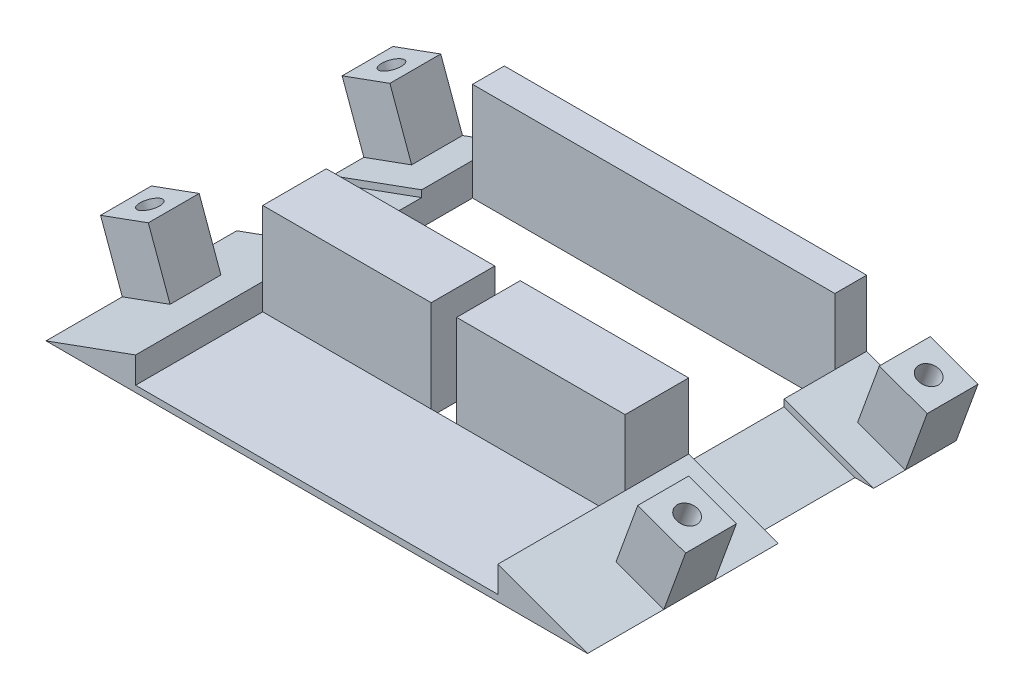
SolidWorks part; units mm, degrees
ref_plane "Front Plane" through (0, 0, 0) normal (0, 0, 1) x (1, 0, 0)
ref_plane "Top Plane" through (0, 0, 0) normal (0, 1, 0) x (1, 0, 0)
ref_plane "Right Plane" through (0, 0, 0) normal (1, 0, 0) x (0, 0, -1)
ref_plane "Plane2" through (28.5, 0, 0) normal (1, 0, 0) x (0, 0, -1)
sketch "Sketch2" plane through (0, 0, 0) normal (0, 0, 1) x (1, 0, 0)
  line L0 (-14.0954, 0) -> (0, 5.1303)
  line L1 (0, 5.1303) -> (0, 0)
  line L2 (-14.0954, 0) -> (0, 0)
  line L3 (28.5, -10.175) -> (28.5, 10.175) construction
  line L4 (71.0954, 0) -> (57, 5.1303)
  line L5 (57, 5.1303) -> (57, 0)
  line L6 (71.0954, 0) -> (57, 0)
  dimension "D1" = 20
  dimension "D2" = 15
extrude "Boss-Extrude1" add sketch "Sketch2" along normal blind 30 and the other way blind 28
sketch "Sketch3" plane through (0, 0, 0) normal (0, 0, 1) x (1, 0, 0)
  line L1 (57, 0) -> (0, 0)
  line L2 (57, 0) -> (57, 15.5)
  line L3 (57, 15.5) -> (0, 15.5)
  line L4 (0, 0) -> (0, 15.5)
  dimension "D1" = 15.5
extrude "Boss-Extrude2" add sketch "Sketch3" along normal blind 10
ref_plane "Plane3" through (0, 0, 15) normal (0, 0, -1) x (-1, 0, 0)
ref_plane "Plane4" through (0, 0, -23) normal (0, 0, 1) x (1, 0, 0)
sketch "Sketch4" plane through (0, 0, -23) normal (0, 0, 1) x (1, 0, 0)
  line L1 (57, 0) -> (0, 0)
  line L2 (57, 0) -> (57, 15.5)
  line L3 (57, 15.5) -> (0, 15.5)
  line L4 (0, 0) -> (0, 15.5)
  line L6 (28.5, -8.525) -> (28.5, 8.525) construction
  point P4 (28.5, 0)
  dimension "D1" = 15.5
extrude "Boss-Extrude3" add sketch "Sketch4" against normal blind 5 separate body
sketch "Sketch5" plane through (0, 0, 0) normal (0, 1, 0) x (1, 0, 0)
  line L1 (71.0954, 28) -> (-14.0954, 28)
  line L2 (71.0954, 28) -> (71.0954, -30)
  line L3 (71.0954, -30) -> (-14.0954, -30)
  line L4 (-14.0954, 28) -> (-14.0954, -30)
ref_plane "Plane5" through (0, 0, 0) normal (-1, 0, 0) x (0, 0, 1)
sketch "Sketch8" plane through (-1.6488, 4.5302, 0) normal (-0.342, 0.9397, 0) x (0.9397, 0.342, 0)
  line L1 (-13.2453, 28) -> (-5.2453, 28)
  line L2 (-13.2453, 28) -> (-13.2453, 20)
  line L3 (-13.2453, 20) -> (-5.2453, 20)
  line L4 (-5.2453, 28) -> (-5.2453, 20)
  line L5 (1.7547, 28) -> (-13.2453, 28) construction
  dimension "D1" = 8
  dimension "D2" = 8
extrude "Boss-Extrude7" add sketch "Sketch8" along normal blind 10
sketch "Sketch9" plane through (-5.069, 13.9271, 0) normal (-0.342, 0.9397, 0) x (0.9397, 0.342, 0)
  line L0 (-5.2453, 28) -> (-13.2453, 28) construction
  line L1 (-13.2453, 28) -> (-13.2453, 20) construction
  circle A0 centre (-9.2453, 24) radius 1.65
  point P4 (-9.2453, 28)
  dimension "D1" = 3.3
  dimension "D2" = 4
  dimension "D3" = 4
extrude "Cut-Extrude1" cut sketch "Sketch9" against normal blind 10
sketch "Sketch10" plane through (8.3166, 22.8496, 0) normal (0.342, 0.9397, 0) x (0.9397, -0.342, 0)
  line L1 (66.8078, 28) -> (58.8078, 28)
  line L2 (66.8078, 28) -> (66.8078, 20)
  line L3 (66.8078, 20) -> (58.8078, 20)
  line L4 (58.8078, 28) -> (58.8078, 20)
  dimension "D1" = 8
  dimension "D2" = 8
extrude "Boss-Extrude8" add sketch "Sketch10" along normal blind 10
sketch "Sketch11" plane through (11.7368, 32.2465, 0) normal (0.342, 0.9397, 0) x (0.9397, -0.342, 0)
  line L1 (66.8078, 20) -> (66.8078, 28) construction
  line L2 (66.8078, 28) -> (58.8078, 28) construction
  circle A0 centre (62.8078, 24) radius 1.65
  dimension "D1" = 3.3
  dimension "D2" = 4
  dimension "D3" = 4
extrude "Cut-Extrude2" cut sketch "Sketch11" against normal blind 10
ref_axis "Axis1" through (0, 0, -30.9) along (0, 0, 1)
sketch "Sketch12" plane through (0, 0, 0) normal (0, 1, 0) x (1, 0, 0)
  line L1 (57, -10) -> (0, -10)
  line L2 (57, -10) -> (57, -30)
  line L3 (57, -30) -> (0, -30)
  line L4 (0, -10) -> (0, -30)
extrude "Boss-Extrude9" add sketch "Sketch12" along normal blind 1
pattern_linear "LPattern5" count 2 spacing 38 along (0, 0, 1) of "Boss-Extrude7", "Cut-Extrude1"
pattern_linear "LPattern6" count 2 spacing 38 along (0, 0, 1) of "Boss-Extrude8", "Cut-Extrude2"
sketch "Sketch13" plane through (0, 0, 0) normal (0, 1, 0) x (1, 0, 0)
  line L1 (26.5, 0) -> (30.5, 0)
  line L2 (26.5, 0) -> (26.5, -10)
  line L3 (26.5, -10) -> (30.5, -10)
  line L4 (30.5, 0) -> (30.5, -10)
  line L5 (0, 0) -> (57, 0) construction
  line L6 (57, -10) -> (0, -10) construction
  point P8 (28.5, 0)
  point P9 (28.5, 0)
  dimension "D1" = 4
extrude "Cut-Extrude3" cut sketch "Sketch13" along normal up to surface (15.5 mm away) up to face at (28.5, 15.5, 5)
sketch "Sketch15" plane through (-1.6488, 4.5302, 0) normal (-0.342, 0.9397, 0) x (0.9397, 0.342, 0)
  line L0 (1.7547, 28) -> (1.7547, 0) construction
  line L1 (1.7547, 15) -> (-13.2453, 15)
  line L2 (1.7547, 15) -> (1.7547, 0)
  line L3 (1.7547, 0) -> (-13.2453, 0)
  line L4 (-13.2453, 15) -> (-13.2453, 0)
  line L5 (-13.2453, 28) -> (-13.2453, -30) construction
  line L6 (5.3013, 0) -> (1.7547, 0) construction
  dimension "D1" = 15
extrude "Cut-Extrude4" cut sketch "Sketch15" against normal blind 1 contours L1 L4 L3 L2
mirror "Mirror5" about plane through (28.5, 0, 0) normal (1, 0, 0) of "Cut-Extrude4"
